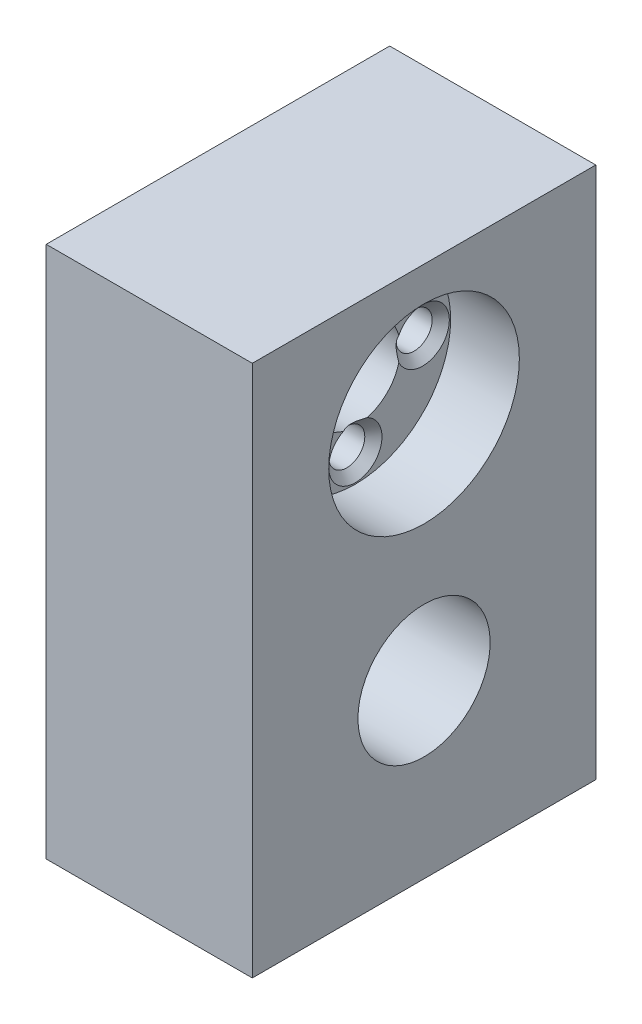
SolidWorks part; units mm, degrees
ref_plane "Front Plane" through (0, 0, 0) normal (0, 0, 1) x (1, 0, 0)
ref_plane "Top Plane" through (0, 0, 0) normal (0, 1, 0) x (1, 0, 0)
ref_plane "Right Plane" through (0, 0, 0) normal (1, 0, 0) x (0, 0, -1)
sketch "Sketch1" plane through (0, 0, 0) normal (0, 1, 0) x (1, 0, 0)
  line L0 (-12, -20) -> (-12, 20)
  line L1 (-12, -20) -> (12, -20)
  line L2 (-12, 20) -> (12, 20)
  line L3 (12, -20) -> (12, 20)
  line L4 (-12, -20) -> (12, 20) construction
  line L5 (-12, 20) -> (12, -20) construction
  point P1 (0, 0)
  dimension "D1" = 40
  dimension "D2" = 24
extrude "Boss-Extrude1" add sketch "Sketch1" along normal blind 62
sketch "Sketch2" plane through (-12, 0, 0) normal (-1, 0, 0) x (0, 0, 1)
  line L0 (-20, 0) -> (20, 0) construction
  circle A0 centre (0, 20) radius 16.2
  point P2 (0, 19.8881)
  dimension "D1" = 32.4
  dimension "D2" = 20
extrude "Cut-Extrude1" cut sketch "Sketch2" against normal blind 5
sketch "Sketch3" plane through (-7, 0, 0) normal (-1, 0, 0) x (0, 0, 1)
  circle A0 centre (0, 20) radius 7.7
  dimension "D1" = 15.4
extrude "Cut-Extrude2" cut sketch "Sketch3" against normal blind 25
sketch "Sketch4" plane through (-7, 0, 0) normal (-1, 0, 0) x (0, 0, 1)
  line L0 (0, 36.2) -> (0, 27.7) construction
  circle A0 centre (0, 31.95) radius 2.1
  circle A1 centre (0, 20) radius 16.2 construction
  circle A2 centre (0, 20) radius 16.2 construction
  circle A3 centre (0, 20) radius 7.7 construction
  point P11 (0, 31.95)
  point P12 (0, 31.75)
  dimension "D1" = 4.2
extrude "Cut-Extrude3" cut sketch "Sketch4" against normal blind 6
chamfer "Chamfer1" distance 1 angle 45 1 edges at (-7, 31.95, 2.1)
pattern_circular "CirPattern1" count 4 over 360 about axis through (-7, 20, 0) along (-1, 0, 0) of "Cut-Extrude3", "Chamfer1"
sketch "Sketch5" plane through (12, 0, 0) normal (1, 0, 0) x (0, 0, -1)
  line L0 (-20, 62) -> (20, 62) construction
  circle A0 centre (0, 46.9) radius 11.1
  point P2 (1.1834, 70.2245)
  point P3 (0, 0)
  dimension "D1" = 22.2
  dimension "D2" = 15.1
extrude "Cut-Extrude4" cut sketch "Sketch5" against normal blind 8
sketch "Sketch6" plane through (4, 0, 0) normal (1, 0, 0) x (0, 0, -1)
  circle A0 centre (0, 46.9) radius 5.25
  dimension "D1" = 10.5
extrude "Cut-Extrude5" cut sketch "Sketch6" against normal up to surface (10.02 mm away)
sketch "Sketch7" plane through (-6.02, 0, 0) normal (1, 0, 0) x (0, 0, -1)
  circle A0 centre (0, 46.9) radius 4.2
  dimension "D1" = 8.4
extrude "Cut-Extrude6" cut sketch "Sketch7" against normal up to surface (5.98 mm away) up to face at (-12, 20, 16.2)
sketch "Sketch8" plane through (4, 0, 0) normal (1, 0, 0) x (0, 0, -1)
  circle A0 centre (0, 54.7452) radius 2.1
  dimension "D1" = 4.2
extrude "Cut-Extrude7" cut sketch "Sketch8" against normal blind 6
chamfer "Chamfer2" distance 1 angle 45 1 edges at (4, 54.7452, -2.1)
pattern_circular "CirPattern2" count 4 over 360 about axis through (-6.02, 46.9, 0) along (1, 0, 0) of "Chamfer2", "Cut-Extrude7"
